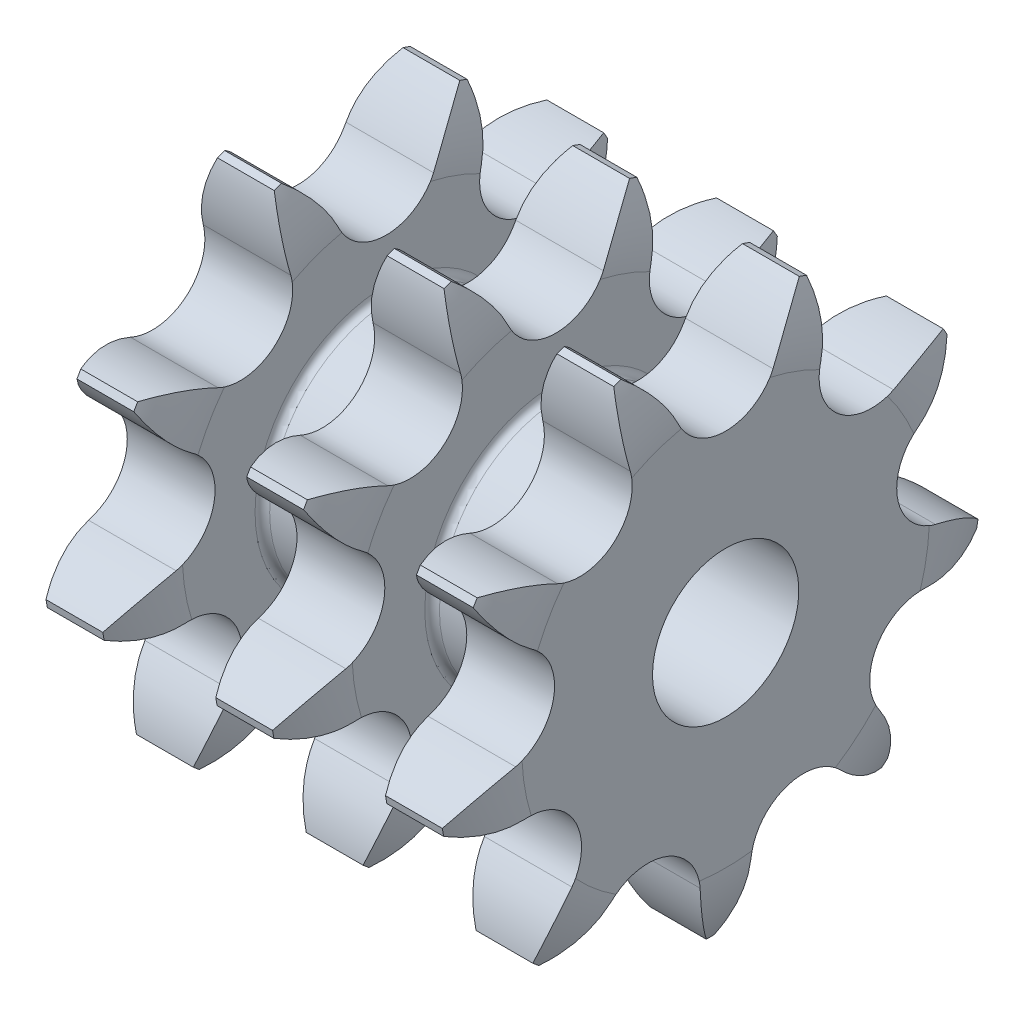
SolidWorks part; units mm, degrees
ref_plane "Plane1" through (0, 0, 0) normal (0, 0, 1) x (1, 0, 0)
ref_plane "Plane2" through (0, 0, 0) normal (0, 1, 0) x (1, 0, 0)
ref_plane "Plane3" through (0, 0, 0) normal (1, 0, 0) x (0, 0, -1)
sketch "Clipboard" plane through (0, 0, 0) normal (0, 1, 0) x (1, 0, 0)
  line L0 (0, 0) -> (12.5436, -1.9867)
  line L1 (-15, 0) -> (100, 0) construction
  line L2 (0, 0) -> (-0.8416, 0.9512)
  line L3 (0, 0) -> (-11.863, 4.5341)
  line L4 (0, 0) -> (3.0618, 0.4849)
  line L5 (0, 0) -> (-2.8109, -1.0484)
  line L6 (0, 0) -> (-29.0469, -19.598)
  line L7 (-0.8416, 0.9512) -> (35.5852, 8.6939)
  line L8 (-76.2, 38.1) -> (-75.2, 38.1)
  line L9 (-73.4259, 41.6592) -> (-72.8306, 41.7344)
  line L10 (-73.4741, 12.7512) -> (-59.5541, 12.7512)
  circle A0 centre (0, 0) radius 4.255
  circle A1 centre (0, 0) radius 10.1515
  circle A2 centre (0, 0) radius 25
  dimension "Num_teeth" = 9
  dimension "Thickness" = 35.04
  dimension "Fillet_rad" = 0.6
sketch "BasProSke" plane through (0, 0, 0) normal (0, 1, 0) x (1, 0, 0)
  line L0 (-10, 0) -> (60, 0) construction
  line L1 (0, 0) -> (0, 16.7129)
  line L2 (0, 0) -> (35.04, 0)
  line L3 (35.04, 0) -> (35.04, 16.7129)
  line L4 (33.77, 22.2487) -> (1.27, 22.2487)
  arc A0 (0, 16.7129) -> (1.27, 22.2487) centre (12.7, 16.7129) cw
  arc A1 (35.04, 16.7129) -> (33.77, 22.2487) centre (22.34, 16.7129) ccw
  dimension "D1" = 12.7
  dimension "Thickness" = 35.04
  dimension "Diameter" = 44.4973
  dimension "G1" = 1.27
revolve "Base-Revolve" add sketch "BasProSke" angle 360 about L0
sketch "GrvSke" plane through (0, 0, 0) normal (0, 1, 0) x (1, 0, 0)
  line L0 (7.2, 16.7129) -> (7.2, 10.7515)
  line L1 (7.8, 10.1515) -> (13.32, 10.1515)
  line L2 (13.92, 10.7515) -> (13.92, 16.7129)
  line L3 (5.93, 22.2487) -> (15.19, 22.2487)
  line L4 (10.56, 0) -> (10.56, 52.07) construction
  line L5 (-10, 0) -> (60, 0) construction
  line L6 (0, 0) -> (35.56, 0) construction
  arc A0 (13.92, 16.7129) -> (15.19, 22.2487) centre (26.62, 16.7129) cw
  arc A1 (7.2, 16.7129) -> (5.93, 22.2487) centre (-5.5, 16.7129) ccw
  arc A2 (7.2, 10.7515) -> (7.8, 10.1515) centre (7.8, 10.7515) ccw
  arc A3 (13.32, 10.1515) -> (13.92, 10.7515) centre (13.32, 10.7515) ccw
  dimension "D1" = 12.7
  dimension "Diameter" = 44.4973
  dimension "Fillet_rad" = 0.6
  dimension "G1" = 1.27
  dimension "Grv_width" = 6.72
revolve "Groove" cut sketch "GrvSke" angle 360 about L6
pattern_linear "Grooves" count 2 spacing 13.92 along (1, 0, 0) of "Groove"
sketch "TooCutSke" plane through (0, 0, 0) normal (1, 0, 0) x (0, 0, -1)
  line L0 (0, 18.6087) -> (3.8949, 16.7925) construction
  line L1 (0, 0) -> (0, 107) construction
  line L2 (0, 18.6087) -> (-10, 18.6087) construction
  line L3 (0, 18.6087) -> (-3.8949, 16.7925) construction
  arc A0 (3.8949, 16.7925) -> (7.8075, 21.3669) centre (14.0756, 12.0451) cw
  arc A1 (3.8949, 16.7925) -> (-3.8949, 16.7925) centre (0, 18.6087) cw
  arc A2 (-3.8949, 16.7925) -> (-7.8075, 21.3669) centre (-14.0756, 12.0451) ccw
  arc A3 (7.8075, 21.3669) -> (-7.8075, 21.3669) centre (0, 0) ccw
extrude "ToothCut" cut sketch "TooCutSke" along normal through all
pattern_circular "TeethCuts" count 9 every 40 about axis through (-10, 0, 0) along (1, 0, 0) of "ToothCut"
sketch "HubNeaOneSke" plane through (0, 0, 0) normal (-1, 0, 0) x (0, 0, 1)
  circle A0 centre (0, 0) radius 10.1515
  dimension "Diameter" = 20.303
extrude "HubNearOne" [suppressed] add sketch "HubNeaOneSke" along normal blind 2.2005
fillet "HubNearOneFillet" [suppressed] radius 0.6
sketch "HubNeaBotSke" plane through (0, 0, 0) normal (-1, 0, 0) x (0, 0, 1)
  circle A0 centre (0, 0) radius 10.1515
  dimension "Diameter" = 20.303
extrude "HubNearBoth" [suppressed] add sketch "HubNeaBotSke" along normal blind 1.1003
fillet "HubNearBothFillet" [suppressed] radius 0.6
ref_plane "FarPln" through (35.04, 0, 0) normal (1, 0, 0) x (0, 0, -1)
sketch "HubFarSke" plane through (35.04, 0, 0) normal (1, 0, 0) x (0, 0, -1)
  circle A0 centre (0, 0) radius 10.1515
  dimension "Diameter" = 20.303
extrude "HubFar" [suppressed] add sketch "HubFarSke" along normal blind 1.1003
fillet "HubFarFillet" [suppressed] radius 0.6
sketch "BorSke" plane through (0, 0, 0) normal (1, 0, 0) x (0, 0, -1)
  circle A0 centre (0, 0) radius 6
  dimension "Diameter" = 12
extrude "Bore" cut sketch "BorSke" along normal mid plane 74.481
sketch "KeySke" plane through (0, 0, 0) normal (1, 0, 0) x (0, 0, -1)
  line L0 (-1, 0) -> (-1, 7)
  line L1 (-1, 7) -> (1, 7)
  line L2 (1, 7) -> (1, 0)
  line L3 (0, 0) -> (0, 34) construction
  line L4 (-1, 0) -> (1, 0)
  dimension "Offset" = 7
  dimension "Width" = 2
extrude "Keyway" [suppressed] cut sketch "KeySke" along normal mid plane 74.481
pattern_circular "Keyway2" [suppressed] count 2 every 90 about axis through (-10, 0, 0) along (1, 0, 0)
equation "' \"Pitch@Clipboard\" = 12.7"
equation "' \"Num_strands@Clipboard\" = 3"
equation "' \"Num_teeth@Clipboard\" = 9"
equation "' \"Hub_dia@Clipboard\" = 50"
equation "' \"Overall_len@Clipboard\" = 3"
equation "' \"Diameter@BorSke\" = 12"
equation "' \"T_dim@Clipboard\" = 1"
equation "' \"Width@KeySke\" = 2"
equation "' \"Dr@Clipboard\" = 8.51"
equation "' \"Face_width@Clipboard\" = 7.2"
equation "' \"Side_radius@Clipboard\" = 12.7"
equation "' \"Side_relief@Clipboard\" = 1.27"
equation "' \"Transv_pitch@Clipboard\" = 13.92"
equation "' \"Show_teeth@Clipboard\" = 9"
equation "' \"Fillet_rad@Clipboard\" = 0.6"
equation "' \"Plate_wid@Clipboard\" = 11.8"
equation "\"Num_teeth@Clipboard\" = int( \"Num_teeth@Clipboard\" )"
equation "\"Num_teeth@Clipboard\" = ((sgn( \"Num_teeth@Clipboard\" - 5.0)+1)*( \"Num_teeth@Clipboard\" - 5.0))/2 +5.0"
equation "\"Num_teeth@Clipboard\" = ((sgn( \"Num_teeth@Clipboard\" - 200.0)-1)*( \"Num_teeth@Clipboard\" - 200.0))/-2 +200.0"
equation "\"MHD@Clipboard\" = \"Pitch@Clipboard\" * (1.0 / tan(3.14159265 / \"Num_teeth@Clipboard\" )) - 1.05 * \"Plate_wid@Clipboard\" - 2.0 * \"Fillet_rad@Clipboard\" - 1.0"
equation "\"Thickness@Clipboard\"  = \"Face_width@Clipboard\" + (\"Num_strands@Clipboard\" - 1) * \"Transv_pitch@Clipboard\""
equation "\"OAL@Clipboard\" = \"Thickness@Clipboard\" + 2 * \"Fillet_rad@Clipboard\" + 1"
equation "\"MHD@Clipboard\" = ((sgn( \"MHD@Clipboard\" - \"Hub_dia@Clipboard\" )-1)*( \"MHD@Clipboard\" - \"Hub_dia@Clipboard\" ))/-2+ \"Hub_dia@Clipboard\""
equation "\"OAL@Clipboard\" = ((sgn( \"OAL@Clipboard\" - \"Overall_len@Clipboard\" )+1)*( \"OAL@Clipboard\" - \"Overall_len@Clipboard\" ))/2 + \"Overall_len@Clipboard\" + 0.0005"
equation "\"Num_teeth@TeethCuts\" = int( \"Show_teeth@Clipboard\" ) + 1"
equation "\"Num_teeth@TeethCuts\" = ((sgn( \"Num_teeth@TeethCuts\" - \"Num_teeth@Clipboard\" )-1)*( \"Num_teeth@TeethCuts\" - \"Num_teeth@Clipboard\" ))/-2+ \"Num_teeth@Clipboard\""
equation "\"Num_teeth@TeethCuts\" = ((sgn( \"Num_teeth@TeethCuts\" - 2.0)+1)*( \"Num_teeth@TeethCuts\" - 2.0))/2 +2.0"
equation "\"Angle@TeethCuts\" = 360.0 / \"Num_teeth@Clipboard\""
equation "\"Seat_radius@TooCutSke\" = ( \"Pitch@Clipboard\" / 2.0) / sin(3.14159265 / \"Num_teeth@Clipboard\" ) - \"Dr@Clipboard\" / 2.0 + \"Dr@Clipboard\" * 0.505"
equation "\"R1@TooCutSke\"  = \"Dr@Clipboard\" * 0.505"
equation "\"X@TooCutSke\" = 140.0 - (90.0 / \"Num_teeth@Clipboard\")"
equation "\"R2@TooCutSke\" = 0.12 * \"Dr@Clipboard\" * ( \"Num_teeth@Clipboard\" + 2.0)"
equation "\"Overcut@TooCutSke\" = 0.5 + 0.625 * \"Pitch@Clipboard\" - 0.5 * \"Dr@Clipboard\"  +  \"Pitch@Clipboard\" / 2.0 / sin(3.14159265 / \"Num_teeth@Clipboard\" )"
equation "\"Diameter@BasProSke\" = 2.0 * ( 0.625 * \"Pitch@Clipboard\" - 0.5 * \"Dr@Clipboard\"  +  \"Pitch@Clipboard\" / 2.0 / sin(3.14159265 / \"Num_teeth@Clipboard\" ))"
equation "\"Thickness@BasProSke\"  = \"Thickness@Clipboard\""
equation "\"G1@BasProSke\" =  \"Side_relief@Clipboard\""
equation "\"G2@BasProSke\" =  \"Side_relief@Clipboard\""
equation "\"D1@BasProSke\" =  \"Side_radius@Clipboard\""
equation "\"Diameter@GrvSke\" = \"Diameter@BasProSke\""
equation "\"G1@GrvSke\" = \"Side_relief@Clipboard\""
equation "\"D1@GrvSke\" = \"Side_radius@Clipboard\""
equation "\"Grv_diam@GrvSke\" =  \"Pitch@Clipboard\" * (1.0 / tan(3.14159265 / \"Num_teeth@Clipboard\" ))- 1.05 * \"Plate_wid@Clipboard\" - 2.0 * \"Fillet_rad@Clipboard\" - 1.0"
equation "\"Grv_width@GrvSke\" =  \"Transv_pitch@Clipboard\" - \"Face_width@Clipboard\""
equation "\"Offset@GrvSke\" = \"Grv_width@GrvSke\" / 2.0 + \"Face_width@Clipboard\""
equation "\"Fillet_rad@GrvSke\" = \"Fillet_rad@Clipboard\""
equation "\"Offset@Grooves\" = \"Transv_pitch@Clipboard\""
equation "\"Num_grvs@Grooves\" = \"Num_strands@Clipboard\""
equation "\"Num_grvs@Grooves\" = \"Num_grvs@Grooves\" - 1 * sgn( \"Num_grvs@Grooves\" -1)"
equation "\"Diameter@HubNeaOneSke\" = \"MHD@Clipboard\""
equation "\"Length@HubNearOne\" = \"OAL@Clipboard\" - \"Thickness@BasProSke\""
equation "\"Diameter@HubNeaBotSke\" = \"MHD@Clipboard\""
equation "\"Length@HubNearBoth\" = ( \"OAL@Clipboard\" - \"Thickness@BasProSke\" ) / 2.0"
equation "\"D1@HubNearOneFillet\" = \"Fillet_rad@Clipboard\""
equation "\"D1@HubNearBothFillet\" = \"Fillet_rad@Clipboard\""
equation "\"Thickness@FarPln\" = \"Thickness@BasProSke\""
equation "\"Diameter@HubFarSke\" = \"MHD@Clipboard\""
equation "\"Length@HubFar\" = ( \"OAL@Clipboard\" - \"Thickness@BasProSke\" ) / 2.0"
equation "\"D1@HubFarFillet\" = \"Fillet_rad@Clipboard\""
equation "\"D1@Bore\" = \"OAL@Clipboard\" * 2.0"
equation "\"D1@Keyway\" = \"OAL@Clipboard\" * 2.0"
equation "\"Offset@KeySke\" = \"T_dim@Clipboard\" + \"Diameter@BorSke\" / 2.0"
